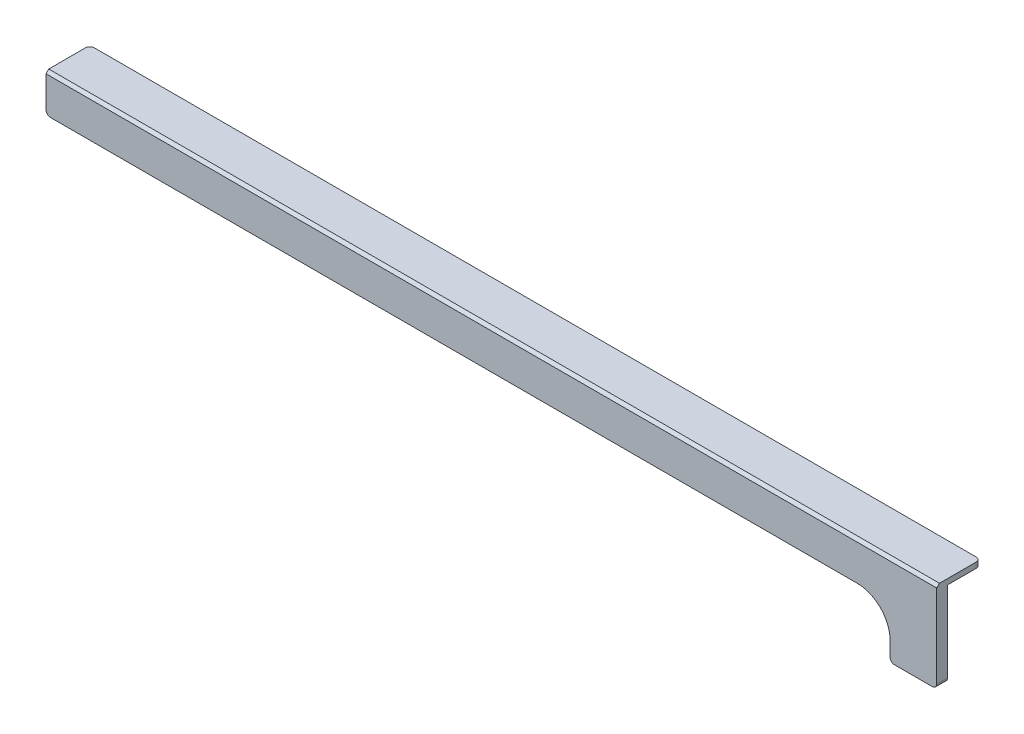
SolidWorks part; units mm, degrees
material "Brass"
ref_plane "Front Plane" through (0, 0, 0) normal (0, 0, 1) x (1, 0, 0)
ref_plane "Top Plane" through (0, 0, 0) normal (0, 1, 0) x (1, 0, 0)
ref_plane "Right Plane" through (0, 0, 0) normal (1, 0, 0) x (0, 0, -1)
ref_plane "Plane1" through (0, 0, 2.6038) normal (0, 0, -1) x (-1, 0, 0)
ref_plane "Plane2" through (0, 63.6237, 0) normal (0, -1, 0) x (-1, 0, 0)
sketch "Sketch1" plane through (0, 63.6237, 0) normal (0, -1, 0) x (-1, 0, 0)
  line L0 (-230.4632, 0) -> (230.4632, 0) construction
  point P4 (0, 0)
sketch "Sketch2" plane through (0, 0, 14.1038) normal (0, 0, 1) x (1, 0, 0)
  line L0 (125.9748, 57.6246) -> (-157.6246, 57.6246) construction
  line L1 (165.5748, 59.6246) -> (-159.2246, 59.6246) construction
  line L4 (163.9748, 38.6744) -> (129.1748, 38.6744) construction
  line L5 (-159.2246, 59.6246) -> (-159.2246, 73.6246)
  line L6 (-159.2246, 73.6246) -> (165.5748, 73.6246)
  line L7 (165.5748, 73.6246) -> (165.5748, 59.6246)
  line L9 (165.5748, 59.6246) -> (165.5748, 40.6744)
  line L10 (165.5748, 40.6744) -> (148.5758, 40.6744)
  line L11 (148.5758, 40.6744) -> (148.5758, 59.6246)
  line L12 (148.5758, 59.6246) -> (-159.2246, 59.6246)
  line L14 (165.5748, -56.0248) -> (165.5748, 37.0744) construction
  line L15 (148.5758, 35.5747) -> (148.5758, 21.5754) construction
  line L18 (-159.2246, 56.0246) -> (-159.2246, 39.6997) construction
  dimension "D1" = 2
  dimension "D3" = 2
extrude "Boss-Extrude1" add sketch "Sketch2" against normal blind 4
sketch "Sketch3" plane through (0, 73.6246, 0) normal (0, 1, 0) x (1, 0, 0)
  line L0 (165.5748, -10.1038) -> (-159.2246, -10.1038) construction
  line L1 (165.5748, -10.1038) -> (-159.2246, -10.1038)
  line L2 (-159.2246, -10.1038) -> (-159.2246, 1.8962)
  line L3 (-159.2246, 1.8962) -> (165.5748, 1.8962)
  line L4 (165.5748, 1.8962) -> (165.5748, -10.1038)
  line L6 (177.5748, -14.1038) -> (131.5748, -14.1038) construction
  dimension "D1" = 16
extrude "Boss-Extrude2" add sketch "Sketch3" against normal blind 2
fillet "Fillet1" radius 1 1 edges at (3.1751, 73.6246, 14.1038) profile chamfer
fillet "Fillet2" radius 1.6 5 edges at (-159.2246, 72.6246, -1.8962) (165.5748, 72.6246, -1.8962) (165.5748, 40.6744, 12.1038) (148.5758, 40.6744, 12.1038) (-159.2246, 59.6246, 12.1038)
fillet "Fillet3" radius 12 1 edges at (148.5758, 59.6246, 12.1038)
hole_wizard "Tap Drill for M3x0.5 Tap1" positions "Sketch4" profile "Sketch5" hole size "M3x0.5" standard "ANSI Metric"
sketch "Sketch4" plane through (0, 0, 5.0798) normal (0, 0, -1) x (-1, 0, 0)
  point P0 (-106.6149, 66.6237)
  point P3 (-37.655, 66.6237)
  point P6 (31.3048, 66.6237)
  point P9 (100.2647, 66.6237)
  point P12 (100.2647, -66.6248)
  point P15 (31.3048, -66.6248)
  point P18 (-37.655, -66.6248)
  point P21 (-106.6149, -66.6248)
sketch "Sketch5" plane through (106.6149, 66.6237, 5.0798) normal (1, 0, 0) x (0, 1, 0)
  line L0 (0, 0) -> (0, 7.7511)
  line L1 (0, 7.7511) -> (1.25, 7)
  line L2 (1.25, 7) -> (1.25, 0.025)
  line L3 (1.25, 0.025) -> (1.275, 0)
  line L4 (1.275, 0) -> (0, 0)
  line L5 (-1.25, 0.025) -> (-1.275, 0) construction
  line L6 (0, 7.7511) -> (-1.25, 7) construction
  line L7 (0, -6.35) -> (0, 107.95) construction
  dimension "Hole Dia." = 2.5
  dimension "Hole Depth" = 7
  dimension "Near C'Sink Dia." = 2.55
  dimension "Near C'Sink Angle" = 90
  dimension "Drill Angle" = 118
hole_wizard "CBORE for M2.5 Hex Socket Head Cap Screw1" positions "Sketch6" profile "Sketch7" counterbore size "M2.5" standard "DIN"
sketch "Sketch6" plane through (0, 0, -6) normal (0, 0, 1) x (1, 0, 0)
  point P0 (-168.5247, -67.1242)
  point P3 (174.8749, -67.1242)
  point P6 (174.8749, 67.1241)
  point P9 (72.135, 67.1241)
  point P12 (-65.7848, 67.1241)
  point P15 (-168.5247, 67.1241)
sketch "Sketch7" plane through (-168.5247, -67.1242, -6) normal (1, 0, 0) x (0, 1, 0)
  line L0 (0, 0) -> (0, 18.8712)
  line L1 (0, 18.8712) -> (1.45, 18)
  line L2 (1.45, 18) -> (1.45, 5.9)
  line L3 (1.45, 5.9) -> (2.75, 5.9)
  line L4 (2.75, 5.9) -> (2.75, 0.025)
  line L5 (2.75, 0.025) -> (2.775, 0)
  line L6 (2.775, 0) -> (0, 0)
  line L7 (-2.75, 0.025) -> (-2.775, 0) construction
  line L8 (0, 18.8712) -> (-1.45, 18) construction
  line L9 (0, -6.35) -> (0, 107.95) construction
  dimension "Hole Dia." = 2.9
  dimension "Hole Depth" = 18
  dimension "C'Bore Dia." = 5.5
  dimension "C'Bore Depth" = 5.9
  dimension "Near C'Sink Dia." = 5.55
  dimension "Near C'Sink Angle" = 90
  dimension "Drill Angle" = 118
